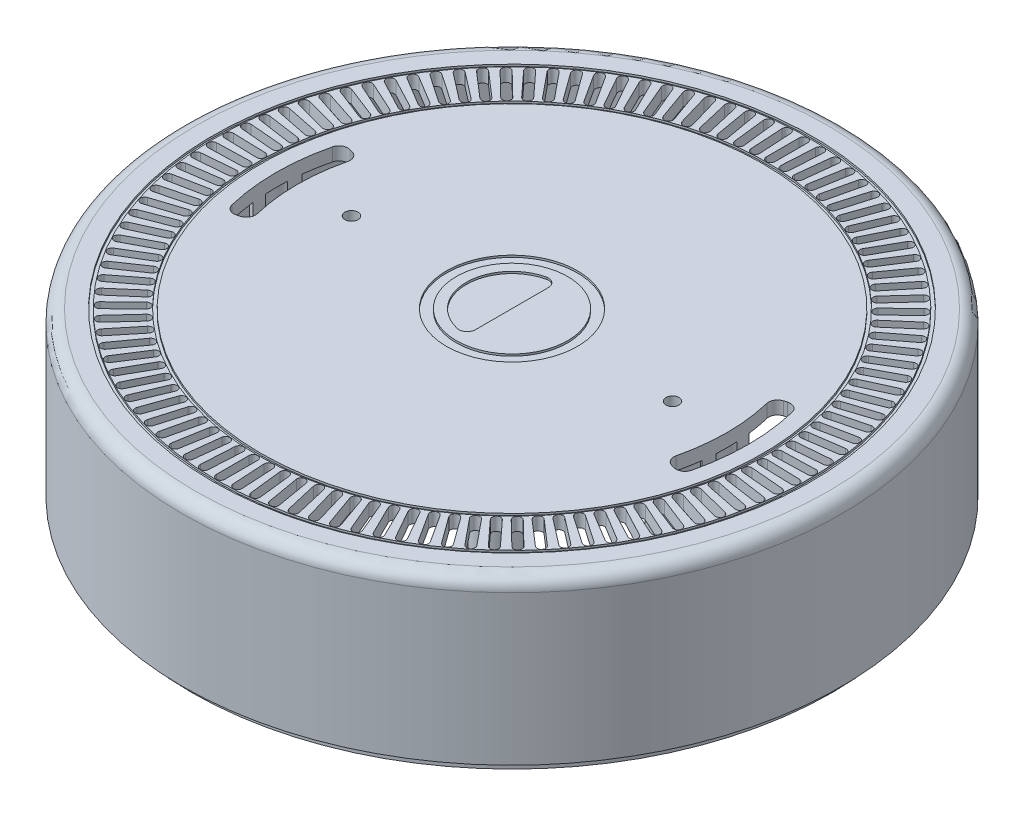
SolidWorks part; units mm, degrees
material "ABS"
ref_plane "Front Plane" through (0, 0, 0) normal (0, 0, 1) x (1, 0, 0)
ref_plane "Top Plane" through (0, 0, 0) normal (0, 1, 0) x (1, 0, 0)
ref_plane "Right Plane" through (0, 0, 0) normal (1, 0, 0) x (0, 0, -1)
sketch "Эскиз1" plane through (0, 0, 0) normal (0, 1, 0) x (1, 0, 0)
  circle A0 centre (0, 0) radius 50
  dimension "D1" = 100
extrude "Бобышка-Вытянуть1" add sketch "Эскиз1" along normal blind 4
shell "Оболочка1" thickness 2
sketch "Эскиз5" plane through (0, 2, 0) normal (0, -1, 0) x (1, 0, 0)
  line L0 (0, 0) -> (23.5, 0) construction
  line L1 (-23.5, 0) -> (-23.5, -26) construction
  line L3 (-23.5, 0) -> (-23.5, 26) construction
  line L4 (-23.5, 0) -> (0, 0) construction
  line L5 (23.5, 0) -> (23.5, 26) construction
  circle A1 centre (-23.5, 26) radius 1.25
  circle A2 centre (-23.5, 26) radius 3
  circle A22 centre (23.5, 26) radius 1.25
  circle A23 centre (23.5, 26) radius 3
  circle A32 centre (23.5, -26) radius 3
  circle A33 centre (23.5, -26) radius 1.25
  circle A34 centre (-23.5, -26) radius 3
  circle A35 centre (-23.5, -26) radius 1.25
  point P25 (-23.5, 26)
extrude "Бобышка-Вытянуть3" add sketch "Эскиз5" along normal blind 22.12
sketch "Эскиз30" plane through (0, 4, 0) normal (0, 1, 0) x (1, 0, 0)
  circle A0 centre (0, 0) radius 50
  circle A1 centre (0, 0) radius 50.3
extrude "Бобышка-Вытянуть15" add sketch "Эскиз30" against normal up to surface (4 mm away) up to face at (0, 0, 48)
fillet "Скругление3" radius 2 1 edges at (0, 4, 50.3)
chamfer "Фаска1" distance 0.3 angle 45 4 edges at (-23.5, -20.12, 24.75) (23.5, -20.12, 24.75) (23.5, -20.12, -24.75) (-23.5, -20.12, -24.75)
sketch "Эскиз34" plane through (0, 4, 0) normal (0, 1, 0) x (1, 0, 0)
  line L0 (-53.661, 25.9683) -> (-78.4097, 1.2195) construction
  line L1 (0, 5.5656) -> (0, -5.5656)
  arc A0 (-1.542, 6.797) -> (0, 5.5656) centre (-1.2626, 5.5656) cw
  arc A1 (-1.542, -6.797) -> (-1.542, 6.797) centre (0, 0) cw
  arc A2 (0, -5.5656) -> (-1.542, -6.797) centre (-1.2626, -5.5656) cw
  circle A3 centre (0, 0) radius 8.4903
  circle A4 centre (0, 0) radius 10
  point P2 (0, 0)
  dimension "D1" = 20
  dimension "D2" = 1.2626
sketch "Эскиз35" plane through (0, 4, 0) normal (0, 1, 0) x (1, 0, 0)
  circle A1 centre (0, 0) radius 45.2
  circle A2 centre (0, 0) radius 38.8
  circle A3 centre (0, 0) radius 38.3
  circle A4 centre (0, 0) radius 45.7
sketch "Эскиз38" plane through (0, 0, 0) normal (0, -1, 0) x (1, 0, 0)
  circle A0 centre (0, 0) radius 48 construction
  circle A1 centre (0, 0) radius 48
  circle A2 centre (0, 0) radius 50.3 construction
  circle A3 centre (0, 0) radius 50.3
extrude "Бобышка-Вытянуть21" add sketch "Эскиз38" along normal blind 28
sketch "Эскиз44" plane through (0, -28, 0) normal (0, -1, 0) x (1, 0, 0)
  circle A0 centre (0, 0) radius 48 construction
  circle A1 centre (0, 0) radius 48
  circle A3 centre (0, 0) radius 50.3 construction
  circle A4 centre (0, 0) radius 50.3
extrude "Вырез-Вытянуть6" cut sketch "Эскиз44" against normal blind 5.7
sketch "Эскиз45" plane through (0, 4, 0) normal (0, 1, 0) x (1, 0, 0)
  line L4 (0, 0) -> (36, 0) construction
  line L6 (0, 0) -> (0, 8.4393) construction
  line L19 (32.9381, -8.5359) -> (33.4212, -8.6653)
  line L20 (32.9381, 8.5359) -> (33.4212, 8.6653)
  line L21 (-32.9381, 8.5359) -> (-33.4212, 8.6653)
  line L22 (-32.9381, -8.5359) -> (-33.4212, -8.6653)
  circle A12 centre (0, 0) radius 48.3 construction
  arc A45 (33.4212, -8.6653) -> (35.0826, -7.6793) centre (33.7706, -7.3613) ccw
  arc A46 (35.0826, 7.6793) -> (35.0826, -7.6793) centre (3.4, 0) cw
  arc A47 (35.0826, 7.6793) -> (33.4212, 8.6653) centre (33.7706, 7.3613) ccw
  arc A48 (32.9381, 8.5359) -> (31.9754, 6.9144) centre (33.2875, 7.2319) ccw
  arc A49 (31.9754, 6.9144) -> (31.9754, -6.9144) centre (3.4, 0) cw
  arc A50 (32.9381, -8.5359) -> (31.9754, -6.9144) centre (33.2875, -7.2319) cw
  arc A51 (-32.9381, -8.5359) -> (-31.9754, -6.9144) centre (-33.2875, -7.2319) ccw
  arc A52 (-31.9754, 6.9144) -> (-31.9754, -6.9144) centre (-3.4, 0) ccw
  arc A53 (-32.9381, 8.5359) -> (-31.9754, 6.9144) centre (-33.2875, 7.2319) cw
  arc A54 (-35.0826, 7.6793) -> (-33.4212, 8.6653) centre (-33.7706, 7.3613) cw
  arc A55 (-35.0826, 7.6793) -> (-35.0826, -7.6793) centre (-3.4, 0) ccw
  arc A56 (-33.4212, -8.6653) -> (-35.0826, -7.6793) centre (-33.7706, -7.3613) cw
  point P16 (-34.3096, -8.2822)
  point P17 (-34.3096, 8.2822)
  point P27 (34.3096, 8.2822)
  point P28 (34.3096, -8.2822)
  dimension "D1" = 1.35
  dimension "D2" = 32.6
  dimension "D3" = 29.4
  dimension "D4" = 3.4
  dimension "D5" = 31.9754
  dimension "D6" = 32.9381
  dimension "D7" = 34.3096
  dimension "D8" = 8.2822
  dimension "D9" = 8.2822
extrude "Вырез-Вытянуть7" cut sketch "Эскиз45" against normal up to surface (2 mm away) up to face at (-23.5, 2, -23)
extrude "Вырез-Вытянуть9" cut sketch "Эскиз35" against normal blind 0.3 contours A4 A1 | A2 A3
sketch "Эскиз46" plane through (0, 4, 0) normal (0, 1, 0) x (1, 0, 0)
  line L0 (0, 0) -> (0, 7.2041) construction
  circle A2 centre (24.5, 0) radius 1
  circle A3 centre (-24.5, 0) radius 1
extrude "Вырез-Вытянуть10" cut sketch "Эскиз46" against normal blind 10
sketch "Эскиз47" plane through (0, 2, 0) normal (0, -1, 0) x (1, 0, 0)
  line L0 (0, 0) -> (0, -3.6148) construction
  circle A0 centre (-24.5, 0) radius 1
  circle A1 centre (-24.5, 0) radius 3
  circle A2 centre (24.5, 0) radius 3
  circle A3 centre (24.5, 0) radius 1
extrude "Бобышка-Вытянуть22" add sketch "Эскиз47" along normal blind 20.3
sketch "Эскиз51" plane through (0, -22.3, 0) normal (0, -1, 0) x (1, 0, 0)
  circle A0 centre (0, 0) radius 50.3 construction
  circle A1 centre (0, 0) radius 50.3
  circle A2 centre (0, 0) radius 48.9
extrude "Вырез-Вытянуть12" cut sketch "Эскиз51" against normal blind 1.5
sketch "Эскиз57" plane through (0, 2, 0) normal (0, -1, 0) x (1, 0, 0)
  circle A0 centre (-23.5, 26) radius 1.25 construction
  circle A1 centre (-23.5, 26) radius 1.25
  circle A2 centre (-23.5, -26) radius 1.25 construction
  circle A3 centre (-23.5, -26) radius 1.25
  circle A4 centre (23.5, -26) radius 1.25 construction
  circle A5 centre (23.5, -26) radius 1.25
  circle A6 centre (23.5, 26) radius 1.25 construction
  circle A7 centre (23.5, 26) radius 1.25
extrude "Бобышка-Вытянуть23" add sketch "Эскиз57" along normal blind 13
extrude "Вырез-Вытянуть14" cut sketch "Эскиз34" against normal blind 0.3 contours A2 L1 A0 A1 | A4 A3
sketch "Эскиз60" plane through (0, 4, 0) normal (0, 1, 0) x (1, 0, 0)
  line L0 (0, 38.7607) -> (0, 45.2) construction
  line L1 (0, 44.4803) -> (0, 39.4803) construction
  line L2 (0.65, 44.4803) -> (0.65, 39.4803)
  line L3 (-0.65, 44.4803) -> (-0.65, 39.4803)
  line L5 (2.5393, 44.4078) -> (2.2539, 39.4159) construction
  line L6 (3.1883, 44.3707) -> (2.9028, 39.3788)
  line L7 (1.8904, 44.4449) -> (1.6049, 39.4531)
  line L8 (5.0704, 44.1904) -> (4.5004, 39.223) construction
  line L9 (5.7161, 44.1163) -> (5.1462, 39.1489)
  line L10 (4.4246, 44.2645) -> (3.8547, 39.2971)
  line L11 (7.5849, 43.8289) -> (6.7323, 38.9021) construction
  line L12 (8.2254, 43.718) -> (7.3728, 38.7913)
  line L13 (6.9444, 43.9397) -> (6.0918, 39.0129)
  line L14 (10.0747, 43.3244) -> (8.9422, 38.4543) construction
  line L15 (10.7078, 43.1772) -> (9.5753, 38.3071)
  line L16 (9.4415, 43.4716) -> (8.3091, 38.6015)
  line L17 (12.5316, 42.6786) -> (11.1229, 37.8811) construction
  line L18 (13.1552, 42.4954) -> (11.7466, 37.698)
  line L19 (11.9079, 42.8617) -> (10.4992, 38.0642)
  line L20 (14.9476, 41.8936) -> (13.2673, 37.1843) construction
  line L21 (15.5598, 41.6751) -> (13.8795, 36.9659)
  line L22 (14.3354, 42.112) -> (12.6551, 37.4028)
  line L23 (17.3149, 40.9719) -> (15.3685, 36.3663) construction
  line L24 (17.9136, 40.7189) -> (15.9672, 36.1132)
  line L25 (16.7161, 41.2249) -> (14.7698, 36.6193)
  line L26 (19.6257, 39.9166) -> (17.4196, 35.4296) construction
  line L27 (20.209, 39.6298) -> (18.0029, 35.1428)
  line L28 (19.0424, 40.2034) -> (16.8362, 35.7164)
  line L29 (21.8724, 38.7311) -> (19.4138, 34.3773) construction
  line L30 (22.4384, 38.4114) -> (19.9798, 34.0577)
  line L31 (21.3065, 39.0507) -> (18.8478, 34.697)
  line L32 (24.0479, 37.4192) -> (21.3447, 33.213) construction
  line L33 (24.5947, 37.0678) -> (21.8915, 32.8616)
  line L34 (23.5011, 37.7707) -> (20.7979, 33.5644)
  line L35 (26.1449, 35.9853) -> (23.206, 31.9403) construction
  line L36 (26.6707, 35.6033) -> (23.7318, 31.5582)
  line L37 (25.619, 36.3674) -> (22.6801, 32.3223)
  line L38 (28.1566, 34.4341) -> (24.9915, 30.5634) construction
  line L39 (28.6598, 34.0226) -> (25.4947, 30.1519)
  line L40 (27.6534, 34.8455) -> (24.4883, 30.9748)
  line L41 (30.0765, 32.7705) -> (26.6956, 29.0868) construction
  line L42 (30.5554, 32.331) -> (27.1745, 28.6473)
  line L43 (29.5976, 33.21) -> (26.2167, 29.5263)
  line L44 (31.8983, 31) -> (28.3126, 27.5153) construction
  line L45 (32.3513, 30.5339) -> (28.7656, 27.0492)
  line L46 (31.4453, 31.4662) -> (27.8596, 27.9815)
  line L47 (33.616, 29.1284) -> (29.8372, 25.8541) construction
  line L48 (34.0417, 28.6372) -> (30.2629, 25.3629)
  line L49 (33.1903, 29.6197) -> (29.4116, 26.3454)
  line L50 (35.2241, 27.1618) -> (31.2646, 24.1086) construction
  line L51 (35.621, 26.6471) -> (31.6615, 23.5938)
  line L52 (34.8272, 27.6766) -> (30.8676, 24.6233)
  line L53 (36.7173, 25.1066) -> (32.5899, 22.2844) construction
  line L54 (37.0842, 24.5701) -> (32.9568, 21.7478)
  line L55 (36.3504, 25.6432) -> (32.223, 22.821)
  line L56 (38.0907, 22.9695) -> (33.8089, 20.3875) construction
  line L57 (38.4263, 22.4129) -> (34.1446, 19.8309)
  line L58 (37.755, 23.5262) -> (33.4733, 20.9442)
  line L59 (39.3399, 20.7575) -> (34.9177, 18.4242) construction
  line L60 (39.6432, 20.1826) -> (35.221, 17.8493)
  line L61 (39.0365, 21.3324) -> (34.6144, 18.9991)
  line L62 (40.4607, 18.4778) -> (35.9126, 16.4007) construction
  line L63 (40.7308, 17.8865) -> (36.1826, 15.8095)
  line L64 (40.1907, 19.0691) -> (35.6426, 16.992)
  line L65 (41.4496, 16.1378) -> (36.7903, 14.3238) construction
  line L66 (41.6854, 15.5321) -> (37.0261, 13.7181)
  line L67 (41.2138, 16.7435) -> (36.5545, 14.9295)
  line L68 (42.3033, 13.7452) -> (37.548, 12.2001) construction
  line L69 (42.5042, 13.127) -> (37.7489, 11.5819)
  line L70 (42.1024, 14.3634) -> (37.3472, 12.8183)
  line L71 (43.019, 11.3077) -> (38.1833, 10.0366) construction
  line L72 (43.1843, 10.6791) -> (38.3485, 9.408)
  line L73 (42.8538, 11.9364) -> (38.018, 10.6653)
  line L74 (43.5944, 8.8334) -> (38.694, 7.8404) construction
  line L75 (43.7235, 8.1963) -> (38.8231, 7.2034)
  line L76 (43.4653, 9.4704) -> (38.5649, 8.4775)
  line L77 (44.0276, 6.3302) -> (39.0785, 5.6186) construction
  line L78 (44.1201, 5.6868) -> (39.171, 4.9753)
  line L79 (43.9351, 6.9736) -> (38.986, 6.262)
  line L80 (44.3172, 3.8064) -> (39.3355, 3.3785) construction
  line L81 (44.3728, 3.1588) -> (39.3911, 2.7309)
  line L82 (44.2615, 4.454) -> (39.2799, 4.0261)
  line L83 (44.4622, 1.2702) -> (39.4642, 1.1274) construction
  line L84 (44.4808, 0.6204) -> (39.4828, 0.4777)
  line L85 (44.4436, 1.9199) -> (39.4457, 1.7771)
  line L86 (44.4622, -1.2702) -> (39.4642, -1.1274) construction
  line L87 (44.4436, -1.9199) -> (39.4457, -1.7771)
  line L88 (44.4808, -0.6204) -> (39.4828, -0.4777)
  line L89 (44.3172, -3.8064) -> (39.3355, -3.3785) construction
  line L90 (44.2615, -4.454) -> (39.2799, -4.0261)
  line L91 (44.3728, -3.1588) -> (39.3911, -2.7309)
  line L92 (44.0276, -6.3302) -> (39.0785, -5.6186) construction
  line L93 (43.9351, -6.9736) -> (38.986, -6.262)
  line L94 (44.1201, -5.6868) -> (39.171, -4.9753)
  line L95 (43.5944, -8.8334) -> (38.694, -7.8404) construction
  line L96 (43.4653, -9.4704) -> (38.5649, -8.4775)
  line L97 (43.7235, -8.1963) -> (38.8231, -7.2034)
  line L98 (43.019, -11.3077) -> (38.1833, -10.0366) construction
  line L99 (42.8538, -11.9364) -> (38.018, -10.6653)
  line L100 (43.1843, -10.6791) -> (38.3485, -9.408)
  line L101 (42.3033, -13.7452) -> (37.548, -12.2001) construction
  line L102 (42.1024, -14.3634) -> (37.3472, -12.8183)
  line L103 (42.5042, -13.127) -> (37.7489, -11.5819)
  line L104 (41.4496, -16.1378) -> (36.7903, -14.3238) construction
  line L105 (41.2138, -16.7435) -> (36.5545, -14.9295)
  line L106 (41.6854, -15.5321) -> (37.0261, -13.7181)
  line L107 (40.4607, -18.4778) -> (35.9126, -16.4007) construction
  line L108 (40.1907, -19.0691) -> (35.6426, -16.992)
  line L109 (40.7308, -17.8865) -> (36.1826, -15.8095)
  line L110 (39.3399, -20.7575) -> (34.9177, -18.4242) construction
  line L111 (39.0365, -21.3324) -> (34.6144, -18.9991)
  line L112 (39.6432, -20.1826) -> (35.221, -17.8493)
  line L113 (38.0907, -22.9695) -> (33.8089, -20.3875) construction
  line L114 (37.755, -23.5262) -> (33.4733, -20.9442)
  line L115 (38.4263, -22.4129) -> (34.1446, -19.8309)
  line L116 (36.7173, -25.1066) -> (32.5899, -22.2844) construction
  line L117 (36.3504, -25.6432) -> (32.223, -22.821)
  line L118 (37.0842, -24.5701) -> (32.9568, -21.7478)
  line L119 (35.2241, -27.1618) -> (31.2646, -24.1086) construction
  line L120 (34.8272, -27.6766) -> (30.8676, -24.6233)
  line L121 (35.621, -26.6471) -> (31.6615, -23.5938)
  line L122 (33.616, -29.1284) -> (29.8372, -25.8541) construction
  line L123 (33.1903, -29.6197) -> (29.4116, -26.3454)
  line L124 (34.0417, -28.6372) -> (30.2629, -25.3629)
  line L125 (31.8983, -31) -> (28.3126, -27.5153) construction
  line L126 (31.4453, -31.4662) -> (27.8596, -27.9815)
  line L127 (32.3513, -30.5339) -> (28.7656, -27.0492)
  line L128 (30.0765, -32.7705) -> (26.6956, -29.0868) construction
  line L129 (29.5976, -33.21) -> (26.2167, -29.5263)
  line L130 (30.5554, -32.331) -> (27.1745, -28.6473)
  line L131 (28.1566, -34.4341) -> (24.9915, -30.5634) construction
  line L132 (27.6534, -34.8455) -> (24.4883, -30.9748)
  line L133 (28.6598, -34.0226) -> (25.4947, -30.1519)
  line L134 (26.1449, -35.9853) -> (23.206, -31.9403) construction
  line L135 (25.619, -36.3674) -> (22.6801, -32.3223)
  line L136 (26.6707, -35.6033) -> (23.7318, -31.5582)
  line L137 (24.0479, -37.4192) -> (21.3447, -33.213) construction
  line L138 (23.5011, -37.7707) -> (20.7979, -33.5644)
  line L139 (24.5947, -37.0678) -> (21.8915, -32.8616)
  line L140 (21.8724, -38.7311) -> (19.4138, -34.3773) construction
  line L141 (21.3065, -39.0507) -> (18.8478, -34.697)
  line L142 (22.4384, -38.4114) -> (19.9798, -34.0577)
  line L143 (19.6257, -39.9166) -> (17.4196, -35.4296) construction
  line L144 (19.0424, -40.2034) -> (16.8362, -35.7164)
  line L145 (20.209, -39.6298) -> (18.0029, -35.1428)
  line L146 (17.3149, -40.9719) -> (15.3685, -36.3663) construction
  line L147 (16.7161, -41.2249) -> (14.7698, -36.6193)
  line L148 (17.9136, -40.7189) -> (15.9672, -36.1132)
  line L149 (14.9476, -41.8936) -> (13.2673, -37.1843) construction
  line L150 (14.3354, -42.112) -> (12.6551, -37.4028)
  line L151 (15.5598, -41.6751) -> (13.8795, -36.9659)
  line L152 (12.5316, -42.6786) -> (11.1229, -37.8811) construction
  line L153 (11.9079, -42.8617) -> (10.4992, -38.0642)
  line L154 (13.1552, -42.4954) -> (11.7466, -37.698)
  line L155 (10.0747, -43.3244) -> (8.9422, -38.4543) construction
  line L156 (9.4415, -43.4716) -> (8.3091, -38.6015)
  line L157 (10.7078, -43.1772) -> (9.5753, -38.3071)
  line L158 (7.5849, -43.8289) -> (6.7323, -38.9021) construction
  line L159 (6.9444, -43.9397) -> (6.0918, -39.0129)
  line L160 (8.2254, -43.718) -> (7.3728, -38.7913)
  line L161 (5.0704, -44.1904) -> (4.5004, -39.223) construction
  line L162 (4.4246, -44.2645) -> (3.8547, -39.2971)
  line L163 (5.7161, -44.1163) -> (5.1462, -39.1489)
  line L164 (2.5393, -44.4078) -> (2.2539, -39.4159) construction
  line L165 (1.8904, -44.4449) -> (1.6049, -39.4531)
  line L166 (3.1883, -44.3707) -> (2.9028, -39.3788)
  line L167 (0, -44.4803) -> (0, -39.4803) construction
  line L168 (-0.65, -44.4803) -> (-0.65, -39.4803)
  line L169 (0.65, -44.4803) -> (0.65, -39.4803)
  line L170 (-2.5393, -44.4078) -> (-2.2539, -39.4159) construction
  line L171 (-3.1883, -44.3707) -> (-2.9028, -39.3788)
  line L172 (-1.8904, -44.4449) -> (-1.6049, -39.4531)
  line L173 (-5.0704, -44.1904) -> (-4.5004, -39.223) construction
  line L174 (-5.7161, -44.1163) -> (-5.1462, -39.1489)
  line L175 (-4.4246, -44.2645) -> (-3.8547, -39.2971)
  line L176 (-7.5849, -43.8289) -> (-6.7323, -38.9021) construction
  line L177 (-8.2254, -43.718) -> (-7.3728, -38.7913)
  line L178 (-6.9444, -43.9397) -> (-6.0918, -39.0129)
  line L179 (-10.0747, -43.3244) -> (-8.9422, -38.4543) construction
  line L180 (-10.7078, -43.1772) -> (-9.5753, -38.3071)
  line L181 (-9.4415, -43.4716) -> (-8.3091, -38.6015)
  line L182 (-12.5316, -42.6786) -> (-11.1229, -37.8811) construction
  line L183 (-13.1552, -42.4954) -> (-11.7466, -37.698)
  line L184 (-11.9079, -42.8617) -> (-10.4992, -38.0642)
  line L185 (-14.9476, -41.8936) -> (-13.2673, -37.1843) construction
  line L186 (-15.5598, -41.6751) -> (-13.8795, -36.9659)
  line L187 (-14.3354, -42.112) -> (-12.6551, -37.4028)
  line L188 (-17.3149, -40.9719) -> (-15.3685, -36.3663) construction
  line L189 (-17.9136, -40.7189) -> (-15.9672, -36.1132)
  line L190 (-16.7161, -41.2249) -> (-14.7698, -36.6193)
  line L191 (-19.6257, -39.9166) -> (-17.4196, -35.4296) construction
  line L192 (-20.209, -39.6298) -> (-18.0029, -35.1428)
  line L193 (-19.0424, -40.2034) -> (-16.8362, -35.7164)
  line L194 (-21.8724, -38.7311) -> (-19.4138, -34.3773) construction
  line L195 (-22.4384, -38.4114) -> (-19.9798, -34.0577)
  line L196 (-21.3065, -39.0507) -> (-18.8478, -34.697)
  line L197 (-24.0479, -37.4192) -> (-21.3447, -33.213) construction
  line L198 (-24.5947, -37.0678) -> (-21.8915, -32.8616)
  line L199 (-23.5011, -37.7707) -> (-20.7979, -33.5644)
  line L200 (-26.1449, -35.9853) -> (-23.206, -31.9403) construction
  line L201 (-26.6707, -35.6033) -> (-23.7318, -31.5582)
  line L202 (-25.619, -36.3674) -> (-22.6801, -32.3223)
  line L203 (-28.1566, -34.4341) -> (-24.9915, -30.5634) construction
  line L204 (-28.6598, -34.0226) -> (-25.4947, -30.1519)
  line L205 (-27.6534, -34.8455) -> (-24.4883, -30.9748)
  line L206 (-30.0765, -32.7705) -> (-26.6956, -29.0868) construction
  line L207 (-30.5554, -32.331) -> (-27.1745, -28.6473)
  line L208 (-29.5976, -33.21) -> (-26.2167, -29.5263)
  line L209 (-31.8983, -31) -> (-28.3126, -27.5153) construction
  line L210 (-32.3513, -30.5339) -> (-28.7656, -27.0492)
  line L211 (-31.4453, -31.4662) -> (-27.8596, -27.9815)
  line L212 (-33.616, -29.1284) -> (-29.8372, -25.8541) construction
  line L213 (-34.0417, -28.6372) -> (-30.2629, -25.3629)
  line L214 (-33.1903, -29.6197) -> (-29.4116, -26.3454)
  line L215 (-35.2241, -27.1618) -> (-31.2646, -24.1086) construction
  line L216 (-35.621, -26.6471) -> (-31.6615, -23.5938)
  line L217 (-34.8272, -27.6766) -> (-30.8676, -24.6233)
  line L218 (-36.7173, -25.1066) -> (-32.5899, -22.2844) construction
  line L219 (-37.0842, -24.5701) -> (-32.9568, -21.7478)
  line L220 (-36.3504, -25.6432) -> (-32.223, -22.821)
  line L221 (-38.0907, -22.9695) -> (-33.8089, -20.3875) construction
  line L222 (-38.4263, -22.4129) -> (-34.1446, -19.8309)
  line L223 (-37.755, -23.5262) -> (-33.4733, -20.9442)
  line L224 (-39.3399, -20.7575) -> (-34.9177, -18.4242) construction
  line L225 (-39.6432, -20.1826) -> (-35.221, -17.8493)
  line L226 (-39.0365, -21.3324) -> (-34.6144, -18.9991)
  line L227 (-40.4607, -18.4778) -> (-35.9126, -16.4007) construction
  line L228 (-40.7308, -17.8865) -> (-36.1826, -15.8095)
  line L229 (-40.1907, -19.0691) -> (-35.6426, -16.992)
  line L230 (-41.4496, -16.1378) -> (-36.7903, -14.3238) construction
  line L231 (-41.6854, -15.5321) -> (-37.0261, -13.7181)
  line L232 (-41.2138, -16.7435) -> (-36.5545, -14.9295)
  line L233 (-42.3033, -13.7452) -> (-37.548, -12.2001) construction
  line L234 (-42.5042, -13.127) -> (-37.7489, -11.5819)
  line L235 (-42.1024, -14.3634) -> (-37.3472, -12.8183)
  line L236 (-43.019, -11.3077) -> (-38.1833, -10.0366) construction
  line L237 (-43.1843, -10.6791) -> (-38.3485, -9.408)
  line L238 (-42.8538, -11.9364) -> (-38.018, -10.6653)
  line L239 (-43.5944, -8.8334) -> (-38.694, -7.8404) construction
  line L240 (-43.7235, -8.1963) -> (-38.8231, -7.2034)
  line L241 (-43.4653, -9.4704) -> (-38.5649, -8.4775)
  line L242 (-44.0276, -6.3302) -> (-39.0785, -5.6186) construction
  line L243 (-44.1201, -5.6868) -> (-39.171, -4.9753)
  line L244 (-43.9351, -6.9736) -> (-38.986, -6.262)
  line L245 (-44.3172, -3.8064) -> (-39.3355, -3.3785) construction
  line L246 (-44.3728, -3.1588) -> (-39.3911, -2.7309)
  line L247 (-44.2615, -4.454) -> (-39.2799, -4.0261)
  line L248 (-44.4622, -1.2702) -> (-39.4642, -1.1274) construction
  line L249 (-44.4808, -0.6204) -> (-39.4828, -0.4777)
  line L250 (-44.4436, -1.9199) -> (-39.4457, -1.7771)
  line L251 (-44.4622, 1.2702) -> (-39.4642, 1.1274) construction
  line L252 (-44.4436, 1.9199) -> (-39.4457, 1.7771)
  line L253 (-44.4808, 0.6204) -> (-39.4828, 0.4777)
  line L254 (-44.3172, 3.8064) -> (-39.3355, 3.3785) construction
  line L255 (-44.2615, 4.454) -> (-39.2799, 4.0261)
  line L256 (-44.3728, 3.1588) -> (-39.3911, 2.7309)
  line L257 (-44.0276, 6.3302) -> (-39.0785, 5.6186) construction
  line L258 (-43.9351, 6.9736) -> (-38.986, 6.262)
  line L259 (-44.1201, 5.6868) -> (-39.171, 4.9753)
  line L260 (-43.5944, 8.8334) -> (-38.694, 7.8404) construction
  line L261 (-43.4653, 9.4704) -> (-38.5649, 8.4775)
  line L262 (-43.7235, 8.1963) -> (-38.8231, 7.2034)
  line L263 (-43.019, 11.3077) -> (-38.1833, 10.0366) construction
  line L264 (-42.8538, 11.9364) -> (-38.018, 10.6653)
  line L265 (-43.1843, 10.6791) -> (-38.3485, 9.408)
  line L266 (-42.3033, 13.7452) -> (-37.548, 12.2001) construction
  line L267 (-42.1024, 14.3634) -> (-37.3472, 12.8183)
  line L268 (-42.5042, 13.127) -> (-37.7489, 11.5819)
  line L269 (-41.4496, 16.1378) -> (-36.7903, 14.3238) construction
  line L270 (-41.2138, 16.7435) -> (-36.5545, 14.9295)
  line L271 (-41.6854, 15.5321) -> (-37.0261, 13.7181)
  line L272 (-40.4607, 18.4778) -> (-35.9126, 16.4007) construction
  line L273 (-40.1907, 19.0691) -> (-35.6426, 16.992)
  line L274 (-40.7308, 17.8865) -> (-36.1826, 15.8095)
  line L275 (-39.3399, 20.7575) -> (-34.9177, 18.4242) construction
  line L276 (-39.0365, 21.3324) -> (-34.6144, 18.9991)
  line L277 (-39.6432, 20.1826) -> (-35.221, 17.8493)
  line L278 (-38.0907, 22.9695) -> (-33.8089, 20.3875) construction
  line L279 (-37.755, 23.5262) -> (-33.4733, 20.9442)
  line L280 (-38.4263, 22.4129) -> (-34.1446, 19.8309)
  line L281 (-36.7173, 25.1066) -> (-32.5899, 22.2844) construction
  line L282 (-36.3504, 25.6432) -> (-32.223, 22.821)
  line L283 (-37.0842, 24.5701) -> (-32.9568, 21.7478)
  line L284 (-35.2241, 27.1618) -> (-31.2646, 24.1086) construction
  line L285 (-34.8272, 27.6766) -> (-30.8676, 24.6233)
  line L286 (-35.621, 26.6471) -> (-31.6615, 23.5938)
  line L287 (-33.616, 29.1284) -> (-29.8372, 25.8541) construction
  line L288 (-33.1903, 29.6197) -> (-29.4116, 26.3454)
  line L289 (-34.0417, 28.6372) -> (-30.2629, 25.3629)
  line L290 (-31.8983, 31) -> (-28.3126, 27.5153) construction
  line L291 (-31.4453, 31.4662) -> (-27.8596, 27.9815)
  line L292 (-32.3513, 30.5339) -> (-28.7656, 27.0492)
  line L293 (-30.0765, 32.7705) -> (-26.6956, 29.0868) construction
  line L294 (-29.5976, 33.21) -> (-26.2167, 29.5263)
  line L295 (-30.5554, 32.331) -> (-27.1745, 28.6473)
  line L296 (-28.1566, 34.4341) -> (-24.9915, 30.5634) construction
  line L297 (-27.6534, 34.8455) -> (-24.4883, 30.9748)
  line L298 (-28.6598, 34.0226) -> (-25.4947, 30.1519)
  line L299 (-26.1449, 35.9853) -> (-23.206, 31.9403) construction
  line L300 (-25.619, 36.3674) -> (-22.6801, 32.3223)
  line L301 (-26.6707, 35.6033) -> (-23.7318, 31.5582)
  line L302 (-24.0479, 37.4192) -> (-21.3447, 33.213) construction
  line L303 (-23.5011, 37.7707) -> (-20.7979, 33.5644)
  line L304 (-24.5947, 37.0678) -> (-21.8915, 32.8616)
  line L305 (-21.8724, 38.7311) -> (-19.4138, 34.3773) construction
  line L306 (-21.3065, 39.0507) -> (-18.8478, 34.697)
  line L307 (-22.4384, 38.4114) -> (-19.9798, 34.0577)
  line L308 (-19.6257, 39.9166) -> (-17.4196, 35.4296) construction
  line L309 (-19.0424, 40.2034) -> (-16.8362, 35.7164)
  line L310 (-20.209, 39.6298) -> (-18.0029, 35.1428)
  line L311 (-17.3149, 40.9719) -> (-15.3685, 36.3663) construction
  line L312 (-16.7161, 41.2249) -> (-14.7698, 36.6193)
  line L313 (-17.9136, 40.7189) -> (-15.9672, 36.1132)
  line L314 (-14.9476, 41.8936) -> (-13.2673, 37.1843) construction
  line L315 (-14.3354, 42.112) -> (-12.6551, 37.4028)
  line L316 (-15.5598, 41.6751) -> (-13.8795, 36.9659)
  line L317 (-12.5316, 42.6786) -> (-11.1229, 37.8811) construction
  line L318 (-11.9079, 42.8617) -> (-10.4992, 38.0642)
  line L319 (-13.1552, 42.4954) -> (-11.7466, 37.698)
  line L320 (-10.0747, 43.3244) -> (-8.9422, 38.4543) construction
  line L321 (-9.4415, 43.4716) -> (-8.3091, 38.6015)
  line L322 (-10.7078, 43.1772) -> (-9.5753, 38.3071)
  line L323 (-7.5849, 43.8289) -> (-6.7323, 38.9021) construction
  line L324 (-6.9444, 43.9397) -> (-6.0918, 39.0129)
  line L325 (-8.2254, 43.718) -> (-7.3728, 38.7913)
  line L326 (-5.0704, 44.1904) -> (-4.5004, 39.223) construction
  line L327 (-4.4246, 44.2645) -> (-3.8547, 39.2971)
  line L328 (-5.7161, 44.1163) -> (-5.1462, 39.1489)
  line L329 (-2.5393, 44.4078) -> (-2.2539, 39.4159) construction
  line L330 (-1.8904, 44.4449) -> (-1.6049, 39.4531)
  line L331 (-3.1883, 44.3707) -> (-2.9028, 39.3788)
  arc A0 (0.65, 44.4803) -> (-0.65, 44.4803) centre (0, 44.4803) ccw
  arc A1 (-0.65, 39.4803) -> (0.65, 39.4803) centre (0, 39.4803) ccw
  circle A2 centre (0, 0) radius 45.2 construction
  circle A3 centre (0, 0) radius 45.2 construction
  arc A4 (3.1883, 44.3707) -> (1.8904, 44.4449) centre (2.5393, 44.4078) ccw
  arc A5 (1.6049, 39.4531) -> (2.9028, 39.3788) centre (2.2539, 39.4159) ccw
  arc A6 (5.7161, 44.1163) -> (4.4246, 44.2645) centre (5.0704, 44.1904) ccw
  arc A7 (3.8547, 39.2971) -> (5.1462, 39.1489) centre (4.5004, 39.223) ccw
  arc A8 (8.2254, 43.718) -> (6.9444, 43.9397) centre (7.5849, 43.8289) ccw
  arc A9 (6.0918, 39.0129) -> (7.3728, 38.7913) centre (6.7323, 38.9021) ccw
  arc A10 (10.7078, 43.1772) -> (9.4415, 43.4716) centre (10.0747, 43.3244) ccw
  arc A11 (8.3091, 38.6015) -> (9.5753, 38.3071) centre (8.9422, 38.4543) ccw
  arc A12 (13.1552, 42.4954) -> (11.9079, 42.8617) centre (12.5316, 42.6786) ccw
  arc A13 (10.4992, 38.0642) -> (11.7466, 37.698) centre (11.1229, 37.8811) ccw
  arc A14 (15.5598, 41.6751) -> (14.3354, 42.112) centre (14.9476, 41.8936) ccw
  arc A15 (12.6551, 37.4028) -> (13.8795, 36.9659) centre (13.2673, 37.1843) ccw
  arc A16 (17.9136, 40.7189) -> (16.7161, 41.2249) centre (17.3149, 40.9719) ccw
  arc A17 (14.7698, 36.6193) -> (15.9672, 36.1132) centre (15.3685, 36.3663) ccw
  arc A18 (20.209, 39.6298) -> (19.0424, 40.2034) centre (19.6257, 39.9166) ccw
  arc A19 (16.8362, 35.7164) -> (18.0029, 35.1428) centre (17.4196, 35.4296) ccw
  arc A20 (22.4384, 38.4114) -> (21.3065, 39.0507) centre (21.8724, 38.7311) ccw
  arc A21 (18.8478, 34.697) -> (19.9798, 34.0577) centre (19.4138, 34.3773) ccw
  arc A22 (24.5947, 37.0678) -> (23.5011, 37.7707) centre (24.0479, 37.4192) ccw
  arc A23 (20.7979, 33.5644) -> (21.8915, 32.8616) centre (21.3447, 33.213) ccw
  arc A24 (26.6707, 35.6033) -> (25.619, 36.3674) centre (26.1449, 35.9853) ccw
  arc A25 (22.6801, 32.3223) -> (23.7318, 31.5582) centre (23.206, 31.9403) ccw
  arc A26 (28.6598, 34.0226) -> (27.6534, 34.8455) centre (28.1566, 34.4341) ccw
  arc A27 (24.4883, 30.9748) -> (25.4947, 30.1519) centre (24.9915, 30.5634) ccw
  arc A28 (30.5554, 32.331) -> (29.5976, 33.21) centre (30.0765, 32.7705) ccw
  arc A29 (26.2167, 29.5263) -> (27.1745, 28.6473) centre (26.6956, 29.0868) ccw
  arc A30 (32.3513, 30.5339) -> (31.4453, 31.4662) centre (31.8983, 31) ccw
  arc A31 (27.8596, 27.9815) -> (28.7656, 27.0492) centre (28.3126, 27.5153) ccw
  arc A32 (34.0417, 28.6372) -> (33.1903, 29.6197) centre (33.616, 29.1284) ccw
  arc A33 (29.4116, 26.3454) -> (30.2629, 25.3629) centre (29.8372, 25.8541) ccw
  arc A34 (35.621, 26.6471) -> (34.8272, 27.6766) centre (35.2241, 27.1618) ccw
  arc A35 (30.8676, 24.6233) -> (31.6615, 23.5938) centre (31.2646, 24.1086) ccw
  arc A36 (37.0842, 24.5701) -> (36.3504, 25.6432) centre (36.7173, 25.1066) ccw
  arc A37 (32.223, 22.821) -> (32.9568, 21.7478) centre (32.5899, 22.2844) ccw
  arc A38 (38.4263, 22.4129) -> (37.755, 23.5262) centre (38.0907, 22.9695) ccw
  arc A39 (33.4733, 20.9442) -> (34.1446, 19.8309) centre (33.8089, 20.3875) ccw
  arc A40 (39.6432, 20.1826) -> (39.0365, 21.3324) centre (39.3399, 20.7575) ccw
  arc A41 (34.6144, 18.9991) -> (35.221, 17.8493) centre (34.9177, 18.4242) ccw
  arc A42 (40.7308, 17.8865) -> (40.1907, 19.0691) centre (40.4607, 18.4778) ccw
  arc A43 (35.6426, 16.992) -> (36.1826, 15.8095) centre (35.9126, 16.4007) ccw
  arc A44 (41.6854, 15.5321) -> (41.2138, 16.7435) centre (41.4496, 16.1378) ccw
  arc A45 (36.5545, 14.9295) -> (37.0261, 13.7181) centre (36.7903, 14.3238) ccw
  arc A46 (42.5042, 13.127) -> (42.1024, 14.3634) centre (42.3033, 13.7452) ccw
  arc A47 (37.3472, 12.8183) -> (37.7489, 11.5819) centre (37.548, 12.2001) ccw
  arc A48 (43.1843, 10.6791) -> (42.8538, 11.9364) centre (43.019, 11.3077) ccw
  arc A49 (38.018, 10.6653) -> (38.3485, 9.408) centre (38.1833, 10.0366) ccw
  arc A50 (43.7235, 8.1963) -> (43.4653, 9.4704) centre (43.5944, 8.8334) ccw
  arc A51 (38.5649, 8.4775) -> (38.8231, 7.2034) centre (38.694, 7.8404) ccw
  arc A52 (44.1201, 5.6868) -> (43.9351, 6.9736) centre (44.0276, 6.3302) ccw
  arc A53 (38.986, 6.262) -> (39.171, 4.9753) centre (39.0785, 5.6186) ccw
  arc A54 (44.3728, 3.1588) -> (44.2615, 4.454) centre (44.3172, 3.8064) ccw
  arc A55 (39.2799, 4.0261) -> (39.3911, 2.7309) centre (39.3355, 3.3785) ccw
  arc A56 (44.4808, 0.6204) -> (44.4436, 1.9199) centre (44.4622, 1.2702) ccw
  arc A57 (39.4457, 1.7771) -> (39.4828, 0.4777) centre (39.4642, 1.1274) ccw
  arc A58 (44.4436, -1.9199) -> (44.4808, -0.6204) centre (44.4622, -1.2702) ccw
  arc A59 (39.4828, -0.4777) -> (39.4457, -1.7771) centre (39.4642, -1.1274) ccw
  arc A60 (44.2615, -4.454) -> (44.3728, -3.1588) centre (44.3172, -3.8064) ccw
  arc A61 (39.3911, -2.7309) -> (39.2799, -4.0261) centre (39.3355, -3.3785) ccw
  arc A62 (43.9351, -6.9736) -> (44.1201, -5.6868) centre (44.0276, -6.3302) ccw
  arc A63 (39.171, -4.9753) -> (38.986, -6.262) centre (39.0785, -5.6186) ccw
  arc A64 (43.4653, -9.4704) -> (43.7235, -8.1963) centre (43.5944, -8.8334) ccw
  arc A65 (38.8231, -7.2034) -> (38.5649, -8.4775) centre (38.694, -7.8404) ccw
  arc A66 (42.8538, -11.9364) -> (43.1843, -10.6791) centre (43.019, -11.3077) ccw
  arc A67 (38.3485, -9.408) -> (38.018, -10.6653) centre (38.1833, -10.0366) ccw
  arc A68 (42.1024, -14.3634) -> (42.5042, -13.127) centre (42.3033, -13.7452) ccw
  arc A69 (37.7489, -11.5819) -> (37.3472, -12.8183) centre (37.548, -12.2001) ccw
  arc A70 (41.2138, -16.7435) -> (41.6854, -15.5321) centre (41.4496, -16.1378) ccw
  arc A71 (37.0261, -13.7181) -> (36.5545, -14.9295) centre (36.7903, -14.3238) ccw
  arc A72 (40.1907, -19.0691) -> (40.7308, -17.8865) centre (40.4607, -18.4778) ccw
  arc A73 (36.1826, -15.8095) -> (35.6426, -16.992) centre (35.9126, -16.4007) ccw
  arc A74 (39.0365, -21.3324) -> (39.6432, -20.1826) centre (39.3399, -20.7575) ccw
  arc A75 (35.221, -17.8493) -> (34.6144, -18.9991) centre (34.9177, -18.4242) ccw
  arc A76 (37.755, -23.5262) -> (38.4263, -22.4129) centre (38.0907, -22.9695) ccw
  arc A77 (34.1446, -19.8309) -> (33.4733, -20.9442) centre (33.8089, -20.3875) ccw
  arc A78 (36.3504, -25.6432) -> (37.0842, -24.5701) centre (36.7173, -25.1066) ccw
  arc A79 (32.9568, -21.7478) -> (32.223, -22.821) centre (32.5899, -22.2844) ccw
  arc A80 (34.8272, -27.6766) -> (35.621, -26.6471) centre (35.2241, -27.1618) ccw
  arc A81 (31.6615, -23.5938) -> (30.8676, -24.6233) centre (31.2646, -24.1086) ccw
  arc A82 (33.1903, -29.6197) -> (34.0417, -28.6372) centre (33.616, -29.1284) ccw
  arc A83 (30.2629, -25.3629) -> (29.4116, -26.3454) centre (29.8372, -25.8541) ccw
  arc A84 (31.4453, -31.4662) -> (32.3513, -30.5339) centre (31.8983, -31) ccw
  arc A85 (28.7656, -27.0492) -> (27.8596, -27.9815) centre (28.3126, -27.5153) ccw
  arc A86 (29.5976, -33.21) -> (30.5554, -32.331) centre (30.0765, -32.7705) ccw
  arc A87 (27.1745, -28.6473) -> (26.2167, -29.5263) centre (26.6956, -29.0868) ccw
  arc A88 (27.6534, -34.8455) -> (28.6598, -34.0226) centre (28.1566, -34.4341) ccw
  arc A89 (25.4947, -30.1519) -> (24.4883, -30.9748) centre (24.9915, -30.5634) ccw
  arc A90 (25.619, -36.3674) -> (26.6707, -35.6033) centre (26.1449, -35.9853) ccw
  arc A91 (23.7318, -31.5582) -> (22.6801, -32.3223) centre (23.206, -31.9403) ccw
  arc A92 (23.5011, -37.7707) -> (24.5947, -37.0678) centre (24.0479, -37.4192) ccw
  arc A93 (21.8915, -32.8616) -> (20.7979, -33.5644) centre (21.3447, -33.213) ccw
  arc A94 (21.3065, -39.0507) -> (22.4384, -38.4114) centre (21.8724, -38.7311) ccw
  arc A95 (19.9798, -34.0577) -> (18.8478, -34.697) centre (19.4138, -34.3773) ccw
  arc A96 (19.0424, -40.2034) -> (20.209, -39.6298) centre (19.6257, -39.9166) ccw
  arc A97 (18.0029, -35.1428) -> (16.8362, -35.7164) centre (17.4196, -35.4296) ccw
  arc A98 (16.7161, -41.2249) -> (17.9136, -40.7189) centre (17.3149, -40.9719) ccw
  arc A99 (15.9672, -36.1132) -> (14.7698, -36.6193) centre (15.3685, -36.3663) ccw
  arc A100 (14.3354, -42.112) -> (15.5598, -41.6751) centre (14.9476, -41.8936) ccw
  arc A101 (13.8795, -36.9659) -> (12.6551, -37.4028) centre (13.2673, -37.1843) ccw
  arc A102 (11.9079, -42.8617) -> (13.1552, -42.4954) centre (12.5316, -42.6786) ccw
  arc A103 (11.7466, -37.698) -> (10.4992, -38.0642) centre (11.1229, -37.8811) ccw
  arc A104 (9.4415, -43.4716) -> (10.7078, -43.1772) centre (10.0747, -43.3244) ccw
  arc A105 (9.5753, -38.3071) -> (8.3091, -38.6015) centre (8.9422, -38.4543) ccw
  arc A106 (6.9444, -43.9397) -> (8.2254, -43.718) centre (7.5849, -43.8289) ccw
  arc A107 (7.3728, -38.7913) -> (6.0918, -39.0129) centre (6.7323, -38.9021) ccw
  arc A108 (4.4246, -44.2645) -> (5.7161, -44.1163) centre (5.0704, -44.1904) ccw
  arc A109 (5.1462, -39.1489) -> (3.8547, -39.2971) centre (4.5004, -39.223) ccw
  arc A110 (1.8904, -44.4449) -> (3.1883, -44.3707) centre (2.5393, -44.4078) ccw
  arc A111 (2.9028, -39.3788) -> (1.6049, -39.4531) centre (2.2539, -39.4159) ccw
  arc A112 (-0.65, -44.4803) -> (0.65, -44.4803) centre (0, -44.4803) ccw
  arc A113 (0.65, -39.4803) -> (-0.65, -39.4803) centre (0, -39.4803) ccw
  arc A114 (-3.1883, -44.3707) -> (-1.8904, -44.4449) centre (-2.5393, -44.4078) ccw
  arc A115 (-1.6049, -39.4531) -> (-2.9028, -39.3788) centre (-2.2539, -39.4159) ccw
  arc A116 (-5.7161, -44.1163) -> (-4.4246, -44.2645) centre (-5.0704, -44.1904) ccw
  arc A117 (-3.8547, -39.2971) -> (-5.1462, -39.1489) centre (-4.5004, -39.223) ccw
  arc A118 (-8.2254, -43.718) -> (-6.9444, -43.9397) centre (-7.5849, -43.8289) ccw
  arc A119 (-6.0918, -39.0129) -> (-7.3728, -38.7913) centre (-6.7323, -38.9021) ccw
  arc A120 (-10.7078, -43.1772) -> (-9.4415, -43.4716) centre (-10.0747, -43.3244) ccw
  arc A121 (-8.3091, -38.6015) -> (-9.5753, -38.3071) centre (-8.9422, -38.4543) ccw
  arc A122 (-13.1552, -42.4954) -> (-11.9079, -42.8617) centre (-12.5316, -42.6786) ccw
  arc A123 (-10.4992, -38.0642) -> (-11.7466, -37.698) centre (-11.1229, -37.8811) ccw
  arc A124 (-15.5598, -41.6751) -> (-14.3354, -42.112) centre (-14.9476, -41.8936) ccw
  arc A125 (-12.6551, -37.4028) -> (-13.8795, -36.9659) centre (-13.2673, -37.1843) ccw
  arc A126 (-17.9136, -40.7189) -> (-16.7161, -41.2249) centre (-17.3149, -40.9719) ccw
  arc A127 (-14.7698, -36.6193) -> (-15.9672, -36.1132) centre (-15.3685, -36.3663) ccw
  arc A128 (-20.209, -39.6298) -> (-19.0424, -40.2034) centre (-19.6257, -39.9166) ccw
  arc A129 (-16.8362, -35.7164) -> (-18.0029, -35.1428) centre (-17.4196, -35.4296) ccw
  arc A130 (-22.4384, -38.4114) -> (-21.3065, -39.0507) centre (-21.8724, -38.7311) ccw
  arc A131 (-18.8478, -34.697) -> (-19.9798, -34.0577) centre (-19.4138, -34.3773) ccw
  arc A132 (-24.5947, -37.0678) -> (-23.5011, -37.7707) centre (-24.0479, -37.4192) ccw
  arc A133 (-20.7979, -33.5644) -> (-21.8915, -32.8616) centre (-21.3447, -33.213) ccw
  arc A134 (-26.6707, -35.6033) -> (-25.619, -36.3674) centre (-26.1449, -35.9853) ccw
  arc A135 (-22.6801, -32.3223) -> (-23.7318, -31.5582) centre (-23.206, -31.9403) ccw
  arc A136 (-28.6598, -34.0226) -> (-27.6534, -34.8455) centre (-28.1566, -34.4341) ccw
  arc A137 (-24.4883, -30.9748) -> (-25.4947, -30.1519) centre (-24.9915, -30.5634) ccw
  arc A138 (-30.5554, -32.331) -> (-29.5976, -33.21) centre (-30.0765, -32.7705) ccw
  arc A139 (-26.2167, -29.5263) -> (-27.1745, -28.6473) centre (-26.6956, -29.0868) ccw
  arc A140 (-32.3513, -30.5339) -> (-31.4453, -31.4662) centre (-31.8983, -31) ccw
  arc A141 (-27.8596, -27.9815) -> (-28.7656, -27.0492) centre (-28.3126, -27.5153) ccw
  arc A142 (-34.0417, -28.6372) -> (-33.1903, -29.6197) centre (-33.616, -29.1284) ccw
  arc A143 (-29.4116, -26.3454) -> (-30.2629, -25.3629) centre (-29.8372, -25.8541) ccw
  arc A144 (-35.621, -26.6471) -> (-34.8272, -27.6766) centre (-35.2241, -27.1618) ccw
  arc A145 (-30.8676, -24.6233) -> (-31.6615, -23.5938) centre (-31.2646, -24.1086) ccw
  arc A146 (-37.0842, -24.5701) -> (-36.3504, -25.6432) centre (-36.7173, -25.1066) ccw
  arc A147 (-32.223, -22.821) -> (-32.9568, -21.7478) centre (-32.5899, -22.2844) ccw
  arc A148 (-38.4263, -22.4129) -> (-37.755, -23.5262) centre (-38.0907, -22.9695) ccw
  arc A149 (-33.4733, -20.9442) -> (-34.1446, -19.8309) centre (-33.8089, -20.3875) ccw
  arc A150 (-39.6432, -20.1826) -> (-39.0365, -21.3324) centre (-39.3399, -20.7575) ccw
  arc A151 (-34.6144, -18.9991) -> (-35.221, -17.8493) centre (-34.9177, -18.4242) ccw
  arc A152 (-40.7308, -17.8865) -> (-40.1907, -19.0691) centre (-40.4607, -18.4778) ccw
  arc A153 (-35.6426, -16.992) -> (-36.1826, -15.8095) centre (-35.9126, -16.4007) ccw
  arc A154 (-41.6854, -15.5321) -> (-41.2138, -16.7435) centre (-41.4496, -16.1378) ccw
  arc A155 (-36.5545, -14.9295) -> (-37.0261, -13.7181) centre (-36.7903, -14.3238) ccw
  arc A156 (-42.5042, -13.127) -> (-42.1024, -14.3634) centre (-42.3033, -13.7452) ccw
  arc A157 (-37.3472, -12.8183) -> (-37.7489, -11.5819) centre (-37.548, -12.2001) ccw
  arc A158 (-43.1843, -10.6791) -> (-42.8538, -11.9364) centre (-43.019, -11.3077) ccw
  arc A159 (-38.018, -10.6653) -> (-38.3485, -9.408) centre (-38.1833, -10.0366) ccw
  arc A160 (-43.7235, -8.1963) -> (-43.4653, -9.4704) centre (-43.5944, -8.8334) ccw
  arc A161 (-38.5649, -8.4775) -> (-38.8231, -7.2034) centre (-38.694, -7.8404) ccw
  arc A162 (-44.1201, -5.6868) -> (-43.9351, -6.9736) centre (-44.0276, -6.3302) ccw
  arc A163 (-38.986, -6.262) -> (-39.171, -4.9753) centre (-39.0785, -5.6186) ccw
  arc A164 (-44.3728, -3.1588) -> (-44.2615, -4.454) centre (-44.3172, -3.8064) ccw
  arc A165 (-39.2799, -4.0261) -> (-39.3911, -2.7309) centre (-39.3355, -3.3785) ccw
  arc A166 (-44.4808, -0.6204) -> (-44.4436, -1.9199) centre (-44.4622, -1.2702) ccw
  arc A167 (-39.4457, -1.7771) -> (-39.4828, -0.4777) centre (-39.4642, -1.1274) ccw
  arc A168 (-44.4436, 1.9199) -> (-44.4808, 0.6204) centre (-44.4622, 1.2702) ccw
  arc A169 (-39.4828, 0.4777) -> (-39.4457, 1.7771) centre (-39.4642, 1.1274) ccw
  arc A170 (-44.2615, 4.454) -> (-44.3728, 3.1588) centre (-44.3172, 3.8064) ccw
  arc A171 (-39.3911, 2.7309) -> (-39.2799, 4.0261) centre (-39.3355, 3.3785) ccw
  arc A172 (-43.9351, 6.9736) -> (-44.1201, 5.6868) centre (-44.0276, 6.3302) ccw
  arc A173 (-39.171, 4.9753) -> (-38.986, 6.262) centre (-39.0785, 5.6186) ccw
  arc A174 (-43.4653, 9.4704) -> (-43.7235, 8.1963) centre (-43.5944, 8.8334) ccw
  arc A175 (-38.8231, 7.2034) -> (-38.5649, 8.4775) centre (-38.694, 7.8404) ccw
  arc A176 (-42.8538, 11.9364) -> (-43.1843, 10.6791) centre (-43.019, 11.3077) ccw
  arc A177 (-38.3485, 9.408) -> (-38.018, 10.6653) centre (-38.1833, 10.0366) ccw
  arc A178 (-42.1024, 14.3634) -> (-42.5042, 13.127) centre (-42.3033, 13.7452) ccw
  arc A179 (-37.7489, 11.5819) -> (-37.3472, 12.8183) centre (-37.548, 12.2001) ccw
  arc A180 (-41.2138, 16.7435) -> (-41.6854, 15.5321) centre (-41.4496, 16.1378) ccw
  arc A181 (-37.0261, 13.7181) -> (-36.5545, 14.9295) centre (-36.7903, 14.3238) ccw
  arc A182 (-40.1907, 19.0691) -> (-40.7308, 17.8865) centre (-40.4607, 18.4778) ccw
  arc A183 (-36.1826, 15.8095) -> (-35.6426, 16.992) centre (-35.9126, 16.4007) ccw
  arc A184 (-39.0365, 21.3324) -> (-39.6432, 20.1826) centre (-39.3399, 20.7575) ccw
  arc A185 (-35.221, 17.8493) -> (-34.6144, 18.9991) centre (-34.9177, 18.4242) ccw
  arc A186 (-37.755, 23.5262) -> (-38.4263, 22.4129) centre (-38.0907, 22.9695) ccw
  arc A187 (-34.1446, 19.8309) -> (-33.4733, 20.9442) centre (-33.8089, 20.3875) ccw
  arc A188 (-36.3504, 25.6432) -> (-37.0842, 24.5701) centre (-36.7173, 25.1066) ccw
  arc A189 (-32.9568, 21.7478) -> (-32.223, 22.821) centre (-32.5899, 22.2844) ccw
  arc A190 (-34.8272, 27.6766) -> (-35.621, 26.6471) centre (-35.2241, 27.1618) ccw
  arc A191 (-31.6615, 23.5938) -> (-30.8676, 24.6233) centre (-31.2646, 24.1086) ccw
  arc A192 (-33.1903, 29.6197) -> (-34.0417, 28.6372) centre (-33.616, 29.1284) ccw
  arc A193 (-30.2629, 25.3629) -> (-29.4116, 26.3454) centre (-29.8372, 25.8541) ccw
  arc A194 (-31.4453, 31.4662) -> (-32.3513, 30.5339) centre (-31.8983, 31) ccw
  arc A195 (-28.7656, 27.0492) -> (-27.8596, 27.9815) centre (-28.3126, 27.5153) ccw
  arc A196 (-29.5976, 33.21) -> (-30.5554, 32.331) centre (-30.0765, 32.7705) ccw
  arc A197 (-27.1745, 28.6473) -> (-26.2167, 29.5263) centre (-26.6956, 29.0868) ccw
  arc A198 (-27.6534, 34.8455) -> (-28.6598, 34.0226) centre (-28.1566, 34.4341) ccw
  arc A199 (-25.4947, 30.1519) -> (-24.4883, 30.9748) centre (-24.9915, 30.5634) ccw
  arc A200 (-25.619, 36.3674) -> (-26.6707, 35.6033) centre (-26.1449, 35.9853) ccw
  arc A201 (-23.7318, 31.5582) -> (-22.6801, 32.3223) centre (-23.206, 31.9403) ccw
  arc A202 (-23.5011, 37.7707) -> (-24.5947, 37.0678) centre (-24.0479, 37.4192) ccw
  arc A203 (-21.8915, 32.8616) -> (-20.7979, 33.5644) centre (-21.3447, 33.213) ccw
  arc A204 (-21.3065, 39.0507) -> (-22.4384, 38.4114) centre (-21.8724, 38.7311) ccw
  arc A205 (-19.9798, 34.0577) -> (-18.8478, 34.697) centre (-19.4138, 34.3773) ccw
  arc A206 (-19.0424, 40.2034) -> (-20.209, 39.6298) centre (-19.6257, 39.9166) ccw
  arc A207 (-18.0029, 35.1428) -> (-16.8362, 35.7164) centre (-17.4196, 35.4296) ccw
  arc A208 (-16.7161, 41.2249) -> (-17.9136, 40.7189) centre (-17.3149, 40.9719) ccw
  arc A209 (-15.9672, 36.1132) -> (-14.7698, 36.6193) centre (-15.3685, 36.3663) ccw
  arc A210 (-14.3354, 42.112) -> (-15.5598, 41.6751) centre (-14.9476, 41.8936) ccw
  arc A211 (-13.8795, 36.9659) -> (-12.6551, 37.4028) centre (-13.2673, 37.1843) ccw
  arc A212 (-11.9079, 42.8617) -> (-13.1552, 42.4954) centre (-12.5316, 42.6786) ccw
  arc A213 (-11.7466, 37.698) -> (-10.4992, 38.0642) centre (-11.1229, 37.8811) ccw
  arc A214 (-9.4415, 43.4716) -> (-10.7078, 43.1772) centre (-10.0747, 43.3244) ccw
  arc A215 (-9.5753, 38.3071) -> (-8.3091, 38.6015) centre (-8.9422, 38.4543) ccw
  arc A216 (-6.9444, 43.9397) -> (-8.2254, 43.718) centre (-7.5849, 43.8289) ccw
  arc A217 (-7.3728, 38.7913) -> (-6.0918, 39.0129) centre (-6.7323, 38.9021) ccw
  arc A218 (-4.4246, 44.2645) -> (-5.7161, 44.1163) centre (-5.0704, 44.1904) ccw
  arc A219 (-5.1462, 39.1489) -> (-3.8547, 39.2971) centre (-4.5004, 39.223) ccw
  arc A220 (-1.8904, 44.4449) -> (-3.1883, 44.3707) centre (-2.5393, 44.4078) ccw
  arc A221 (-2.9028, 39.3788) -> (-1.6049, 39.4531) centre (-2.2539, 39.4159) ccw
  point P0 (0, 41.9803)
  point P4 (0, 41.9803)
  point P10 (0, 45.2)
  point P22 (2.3966, 41.9119)
  point P29 (4.7854, 41.7067)
  point P36 (7.1586, 41.3655)
  point P43 (9.5084, 40.8893)
  point P50 (11.8272, 40.2798)
  point P57 (14.1075, 39.5389)
  point P64 (16.3417, 38.6691)
  point P71 (18.5226, 37.6731)
  point P78 (20.6431, 36.5542)
  point P85 (22.6963, 35.3161)
  point P92 (24.6754, 33.9628)
  point P99 (26.5741, 32.4987)
  point P106 (28.386, 30.9286)
  point P113 (30.1054, 29.2577)
  point P120 (31.7266, 27.4913)
  point P127 (33.2443, 25.6352)
  point P134 (34.6536, 23.6955)
  point P141 (35.9498, 21.6785)
  point P148 (37.1288, 19.5908)
  point P155 (38.1867, 17.4393)
  point P162 (39.12, 15.2308)
  point P169 (39.9257, 12.9726)
  point P176 (40.6011, 10.6722)
  point P183 (41.1442, 8.3369)
  point P190 (41.553, 5.9744)
  point P197 (41.8263, 3.5925)
  point P204 (41.9632, 1.1988)
  point P211 (41.9632, -1.1988)
  point P218 (41.8263, -3.5925)
  point P225 (41.553, -5.9744)
  point P232 (41.1442, -8.3369)
  point P239 (40.6011, -10.6722)
  point P246 (39.9257, -12.9726)
  point P253 (39.12, -15.2308)
  point P260 (38.1867, -17.4393)
  point P267 (37.1288, -19.5908)
  point P274 (35.9498, -21.6785)
  point P281 (34.6536, -23.6955)
  point P288 (33.2443, -25.6352)
  point P295 (31.7266, -27.4913)
  point P302 (30.1054, -29.2577)
  point P309 (28.386, -30.9286)
  point P316 (26.5741, -32.4987)
  point P323 (24.6754, -33.9628)
  point P330 (22.6963, -35.3161)
  point P337 (20.6431, -36.5542)
  point P344 (18.5226, -37.6731)
  point P351 (16.3417, -38.6691)
  point P358 (14.1075, -39.5389)
  point P365 (11.8272, -40.2798)
  point P372 (9.5084, -40.8893)
  point P379 (7.1586, -41.3655)
  point P386 (4.7854, -41.7067)
  point P393 (2.3966, -41.9119)
  point P400 (0, -41.9803)
  point P407 (-2.3966, -41.9119)
  point P414 (-4.7854, -41.7067)
  point P421 (-7.1586, -41.3655)
  point P428 (-9.5084, -40.8893)
  point P435 (-11.8272, -40.2798)
  point P442 (-14.1075, -39.5389)
  point P449 (-16.3417, -38.6691)
  point P456 (-18.5226, -37.6731)
  point P463 (-20.6431, -36.5542)
  point P470 (-22.6963, -35.3161)
  point P477 (-24.6754, -33.9628)
  point P484 (-26.5741, -32.4987)
  point P491 (-28.386, -30.9286)
  point P498 (-30.1054, -29.2577)
  point P505 (-31.7266, -27.4913)
  point P512 (-33.2443, -25.6352)
  point P519 (-34.6536, -23.6955)
  point P526 (-35.9498, -21.6785)
  point P533 (-37.1288, -19.5908)
  point P540 (-38.1867, -17.4393)
  point P547 (-39.12, -15.2308)
  point P554 (-39.9257, -12.9726)
  point P561 (-40.6011, -10.6722)
  point P568 (-41.1442, -8.3369)
  point P575 (-41.553, -5.9744)
  point P582 (-41.8263, -3.5925)
  point P589 (-41.9632, -1.1988)
  point P596 (-41.9632, 1.1988)
  point P603 (-41.8263, 3.5925)
  point P610 (-41.553, 5.9744)
  point P617 (-41.1442, 8.3369)
  point P624 (-40.6011, 10.6722)
  point P631 (-39.9257, 12.9726)
  point P638 (-39.12, 15.2308)
  point P645 (-38.1867, 17.4393)
  point P652 (-37.1288, 19.5908)
  point P659 (-35.9498, 21.6785)
  point P666 (-34.6536, 23.6955)
  point P673 (-33.2443, 25.6352)
  point P680 (-31.7266, 27.4913)
  point P687 (-30.1054, 29.2577)
  point P694 (-28.386, 30.9286)
  point P701 (-26.5741, 32.4987)
  point P708 (-24.6754, 33.9628)
  point P715 (-22.6963, 35.3161)
  point P722 (-20.6431, 36.5542)
  point P729 (-18.5226, 37.6731)
  point P736 (-16.3417, 38.6691)
  point P743 (-14.1075, 39.5389)
  point P750 (-11.8272, 40.2798)
  point P757 (-9.5084, 40.8893)
  point P764 (-7.1586, 41.3655)
  point P771 (-4.7854, 41.7067)
  point P778 (-2.3966, 41.9119)
  point P783 (0, 0)
  dimension "D1" = 110
extrude "Вырез-Вытянуть15" cut sketch "Эскиз60" against normal blind 3
sketch "Эскиз61" plane through (0, 2, 0) normal (0, -1, 0) x (1, 0, 0)
  line L0 (0, 0) -> (0, -8.4611) construction
  arc A0 (35.956, -1.6938) -> (35.956, 1.6938) centre (34.4, 0) ccw
  arc A1 (35.7832, -3.7532) -> (35.7832, 3.7532) centre (34.4, 0) ccw
  arc A2 (35.0826, -7.6793) -> (35.0826, 7.6793) centre (3.4, 0) ccw construction
  arc A3 (35.7832, -3.7532) -> (35.956, -1.6938) centre (3.4, 0) ccw
  arc A4 (31.9754, -6.9144) -> (31.9754, 6.9144) centre (3.4, 0) ccw construction
  arc A5 (32.5832, -3.5636) -> (32.756, -1.6085) centre (3.4, 0) ccw
  arc A6 (32.756, 1.6085) -> (32.756, -1.6085) centre (34.4, 0) ccw
  arc A7 (32.5832, 3.5636) -> (32.5832, -3.5636) centre (34.4, 0) ccw
  arc A8 (32.756, 1.6085) -> (32.5832, 3.5636) centre (3.4, 0) ccw
  arc A9 (35.956, 1.6938) -> (35.7832, 3.7532) centre (3.4, 0) ccw
  arc A10 (-35.956, 1.6938) -> (-35.7832, 3.7532) centre (-3.4, 0) cw
  arc A11 (-32.756, 1.6085) -> (-32.5832, 3.5636) centre (-3.4, 0) cw
  arc A12 (-32.5832, 3.5636) -> (-32.5832, -3.5636) centre (-34.4, 0) cw
  arc A13 (-32.756, 1.6085) -> (-32.756, -1.6085) centre (-34.4, 0) cw
  arc A14 (-32.5832, -3.5636) -> (-32.756, -1.6085) centre (-3.4, 0) cw
  arc A15 (-35.7832, -3.7532) -> (-35.956, -1.6938) centre (-3.4, 0) cw
  arc A16 (-35.7832, -3.7532) -> (-35.7832, 3.7532) centre (-34.4, 0) cw
  arc A17 (-35.956, -1.6938) -> (-35.956, 1.6938) centre (-34.4, 0) cw
  point P18 (0, 0)
  dimension "D1" = 2.3
  dimension "D2" = 4
extrude "Бобышка-Вытянуть24" add sketch "Эскиз61" along normal blind 10
